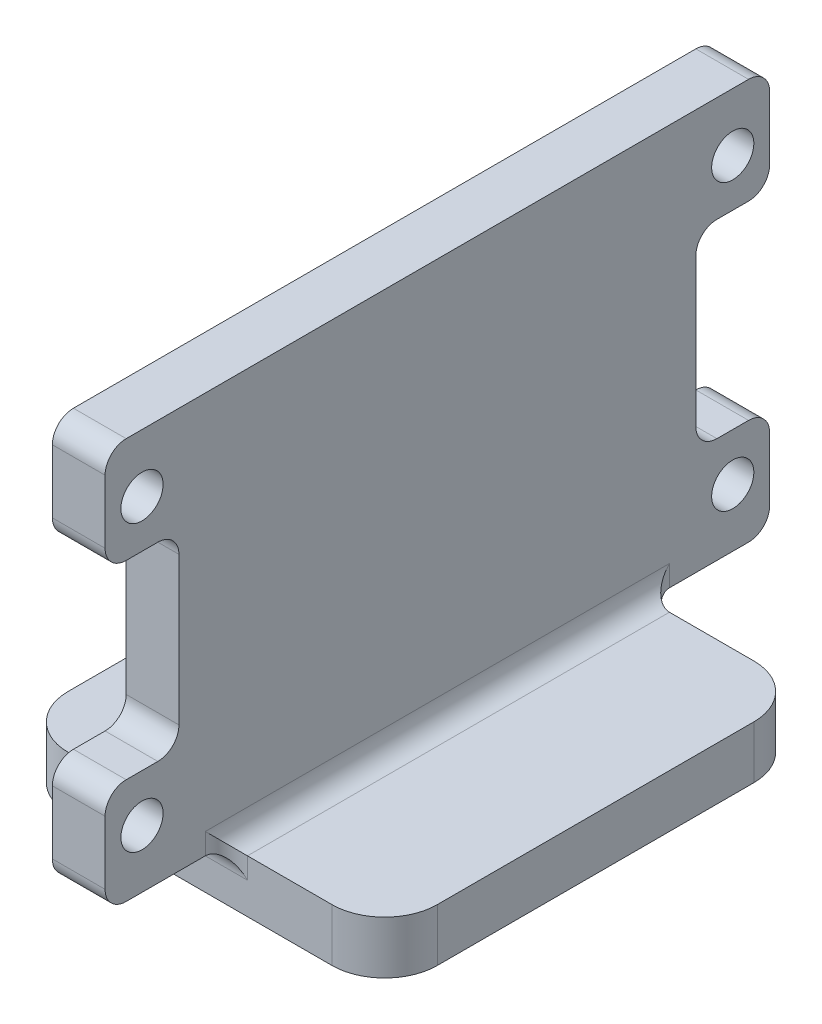
SolidWorks part; units mm, degrees
ref_plane "Plan de face" through (0, 0, 0) normal (0, 0, 1) x (1, 0, 0)
ref_plane "Plan de dessus" through (0, 0, 0) normal (0, 1, 0) x (1, 0, 0)
ref_plane "Plan de droite" through (0, 0, 0) normal (1, 0, 0) x (0, 0, -1)
sketch "Esquisse2" plane through (0, 0, 0) normal (0, 1, 0) x (1, 0, 0)
  line L1 (-17.5, -20) -> (17.5, -20)
  line L2 (-17.5, -20) -> (-17.5, 20)
  line L3 (-17.5, 20) -> (17.5, 20)
  line L4 (17.5, -20) -> (17.5, 20)
  line L5 (-17.5, -20) -> (17.5, 20) construction
  line L6 (-17.5, 20) -> (17.5, -20) construction
  point P0 (0, 0)
  dimension "D1" = 35
  dimension "D2" = 40
extrude "Boss.-Extru.1" add sketch "Esquisse2" along normal blind 5
sketch "Esquisse3" plane through (0, 0, 0) normal (1, 0, 0) x (0, 0, -1)
  line L1 (-31.5, 5) -> (31.5, 5)
  line L2 (-31.5, 5) -> (-31.5, 43)
  line L3 (-31.5, 43) -> (31.5, 43)
  line L4 (31.5, 5) -> (31.5, 43)
  line L5 (0, 5) -> (0, 0) construction
  line L6 (-20, 5) -> (20, 5) construction
  point P8 (-31, 14.0131)
  dimension "D1" = 38
  dimension "D2" = 63
extrude "Boss.-Extru.2" add sketch "Esquisse3" along normal mid plane 5
sketch "Esquisse4" plane through (2.5, 0, 0) normal (1, 0, 0) x (0, 0, -1)
  line L0 (-28, 37.5) -> (-28, 10.5) construction
  line L1 (-28, 10.5) -> (28, 10.5) construction
  line L2 (28, 10.5) -> (28, 37.5) construction
  line L3 (28, 37.5) -> (-28, 37.5) construction
  line L4 (0, 10.5) -> (0, 0) construction
  line L5 (-28, 24) -> (-31.5, 24) construction
  line L6 (-31.5, 43) -> (-31.5, 5) construction
  circle A0 centre (-28, 37.5) radius 2
  circle A1 centre (-28, 10.5) radius 2
  circle A2 centre (28, 37.5) radius 2
  circle A3 centre (28, 10.5) radius 2
  dimension "D1" = 4
  dimension "D2" = 4
  dimension "D3" = 4
  dimension "D4" = 56
  dimension "D5" = 27
extrude "Enlèv. mat.-Extru.1" cut sketch "Esquisse4" against normal up to next
sketch "Esquisse5" plane through (2.5, 0, 0) normal (1, 0, 0) x (0, 0, -1)
  line L0 (-31.5, 43) -> (-31.5, 5) construction
  line L1 (-31.5, 33) -> (-24.5, 33)
  line L2 (-31.5, 33) -> (-31.5, 15)
  line L3 (-31.5, 15) -> (-24.5, 15)
  line L4 (-24.5, 33) -> (-24.5, 15)
  line L5 (-31.5, 24) -> (-24.5, 24) construction
  line L7 (0, 0) -> (0, 16.9686) construction
  line L8 (-20, 0) -> (20, 0) construction
  line L9 (31.5, 15) -> (24.5, 15)
  line L10 (24.5, 33) -> (24.5, 15)
  line L11 (31.5, 33) -> (24.5, 33)
  line L12 (31.5, 33) -> (31.5, 15)
  dimension "D1" = 7
  dimension "D2" = 18
extrude "Enlèv. mat.-Extru.2" cut sketch "Esquisse5" against normal up to next
fillet "Congé1" radius 2 14 edges at (0, 5, -31.5) (0, 15, -24.5) (0, 15, -31.5) (0, 33, -24.5) (0, 43, -31.5) (0, 33, -31.5) (0, 15, 24.5) (0, 5, 31.5) (0, 15, 31.5) (0, 33, 24.5) (0, 33, 31.5) (0, 43, 31.5) (-2.5, 5, 0) (2.5, 5, 0)
fillet "Congé2" radius 5 4 edges at (-17.5, 2.5, 20) (-17.5, 2.5, -20) (17.5, 2.5, 20) (17.5, 2.5, -20)
fillet "Congé3" radius 2 6 edges at (-2.5, 6, 20) (2.5, 6, 20) (0, 5, 20) (2.5, 6, -20) (-2.5, 6, -20) (0, 5, -20)
